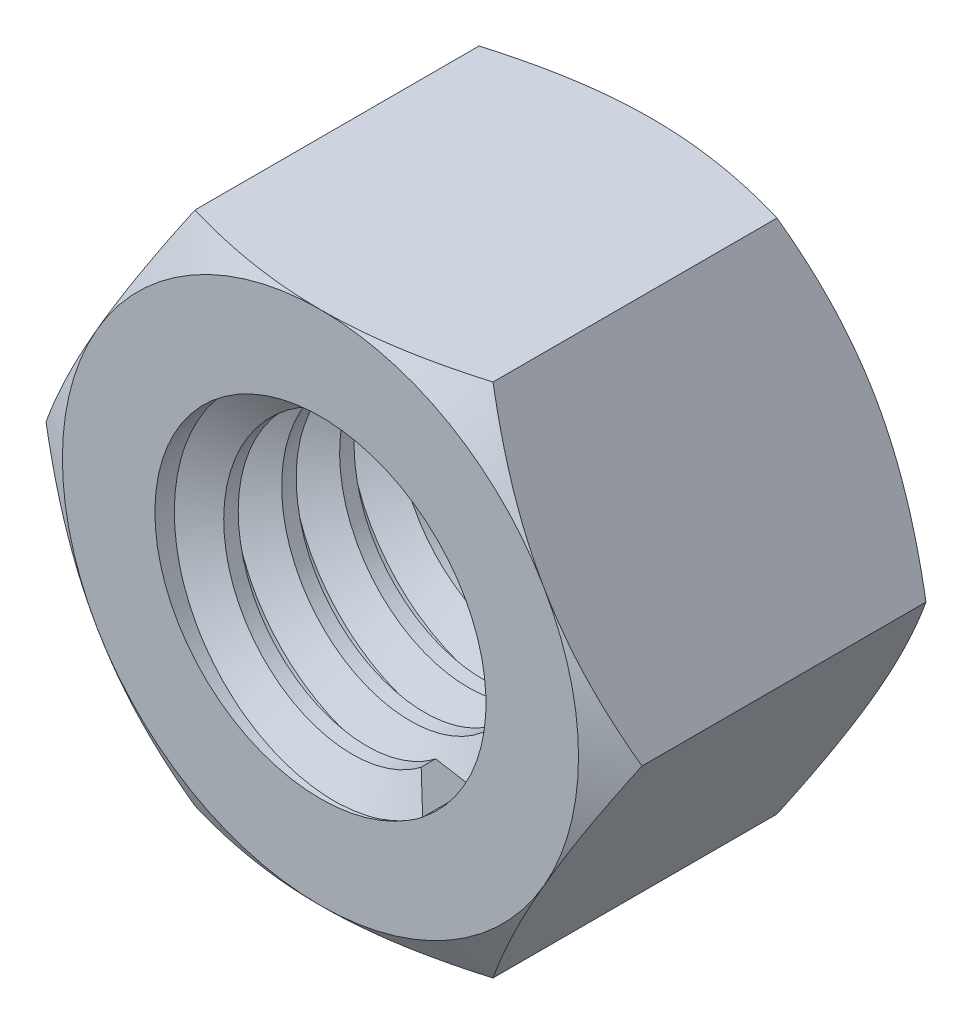
SolidWorks part; units mm, degrees
ref_plane "Front Plane" through (0, 0, 0) normal (0, 0, 1) x (1, 0, 0)
ref_plane "Top Plane" through (0, 0, 0) normal (0, 1, 0) x (1, 0, 0)
ref_plane "Right Plane" through (0, 0, 0) normal (1, 0, 0) x (0, 0, -1)
sketch "Sketch1" plane through (0, 0, 0) normal (0, 0, 1) x (1, 0, 0)
  line L1 (9, 0) -> (4.5, 7.7942)
  line L2 (4.5, 7.7942) -> (-4.5, 7.7942)
  line L3 (-4.5, 7.7942) -> (-9, 0)
  line L4 (-9, 0) -> (-4.5, -7.7942)
  line L5 (-4.5, -7.7942) -> (4.5, -7.7942)
  line L6 (4.5, -7.7942) -> (9, 0)
  circle A0 centre (0, 0) radius 7.7942 construction
  circle A1 centre (0, 0) radius 5
  dimension "D2" = 10
  dimension "D1" = 18
extrude "Boss-Extrude1" add sketch "Sketch1" along normal mid plane 10
sketch "Sketch2" plane through (0, 0, 0) normal (1, 0, 0) x (0, 0, -1)
  line L0 (-5, 7.7942) -> (-5, 12.4591)
  line L1 (-5, 12.4591) -> (-2.2483, 12.4591)
  line L2 (-2.2483, 12.4591) -> (-5, 7.7942)
  line L3 (0, 0) -> (0, 50000) construction
  line L4 (2.2483, 12.4591) -> (5, 7.7942)
  line L5 (5, 7.7942) -> (5, 12.4591)
  line L6 (5, 12.4591) -> (2.2483, 12.4591)
  line L7 (0, 0) -> (50000, 0) construction
  dimension "D1" = 30.535
revolve "Cut-Revolve1" cut sketch "Sketch2" angle 360 about L7
thread "Thread1" pitch 1.75 method extrude profile "Thread Profile1" start angle 0, offset 0, length 8.5, pitch 1.75, diameter 10
ref_plane "Plane1" through (5, 0, -5) normal (0, -1, 0) x (1, 0, 0)
sketch "Thread Profile1" plane through (5, 0, -5) normal (0, -1, 0) x (1, 0, 0)
  line L0 (0, 0) -> (0, 1.75) construction
  line L11 (0, 0) -> (0, 1.5312)
  line L12 (0, 1.5312) -> (-0.9472, 0.9844)
  line L13 (-0.9472, 0.9844) -> (-0.9472, 0.5469)
  line L15 (-0.9472, 0.5469) -> (0, 0)
  line L17 (-0.9472, 0.7656) -> (0, 0.7656) construction
  point P2 (0, 0)
  dimension "Pitch" = 1.75
  dimension "Profile_Angle" = 60
  dimension "Profile_Land" = 0.4375
  dimension "Profile_Height" = 0.9472
